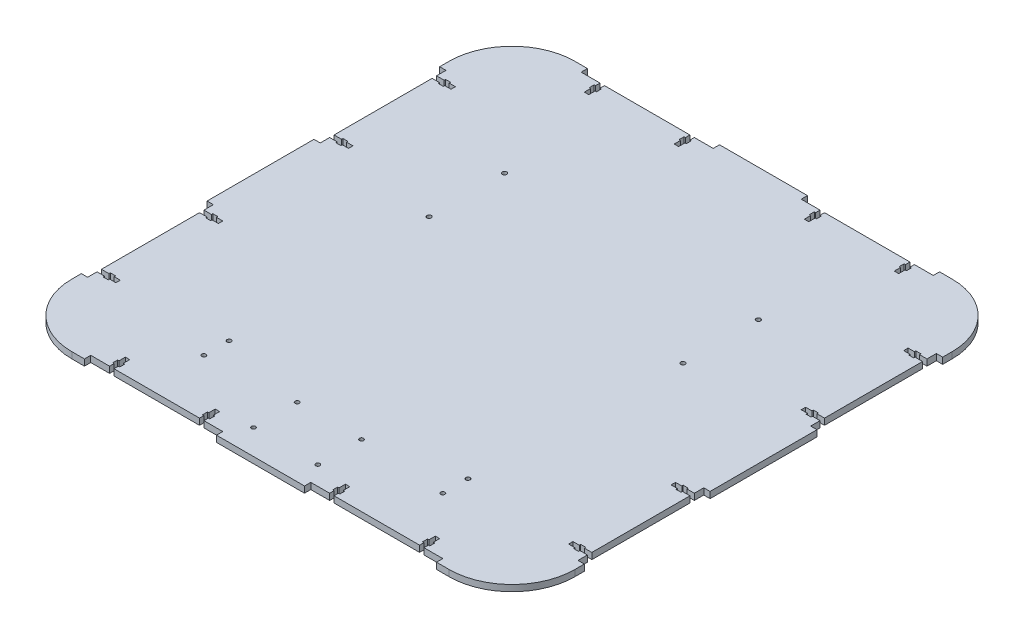
SolidWorks part; units mm, degrees
ref_plane "Front Plane" through (0, 0, 0) normal (0, 0, 1) x (1, 0, 0)
ref_plane "Top Plane" through (0, 0, 0) normal (0, 1, 0) x (1, 0, 0)
ref_plane "Right Plane" through (0, 0, 0) normal (1, 0, 0) x (0, 0, -1)
sketch "Sketch1" plane through (0, 0, 0) normal (0, 1, 0) x (1, 0, 0)
  line L0 (0, -1000) -> (0, 49000) construction
  line L9 (-1000, 0) -> (49000, 0) construction
  line L10 (-10, 190) -> (10, 190) construction
  line L11 (-10, 190) -> (-10, 170) construction
  line L12 (-10, 170) -> (10, 170) construction
  line L13 (10, 190) -> (10, 170) construction
  line L14 (-1010, 180) -> (48990, 180) construction
  line L15 (-1010, -180) -> (48990, -180) construction
  line L16 (0, 1000) -> (0, -49000) construction
  line L17 (-10, -170) -> (10, -170)
  line L18 (10, -190) -> (10, -170)
  line L19 (-10, -190) -> (10, -190)
  line L20 (-10, -190) -> (-10, -170)
  line L22 (-200, 200) -> (200, 200)
  line L23 (-200, 200) -> (-200, -200)
  line L24 (-200, -200) -> (200, -200)
  line L25 (200, 200) -> (200, -200)
  circle A0 centre (0, 0) radius 200 construction
  circle A1 centre (-7.5, 187.5) radius 1.75 construction
  circle A2 centre (7.5, 187.5) radius 1.75 construction
  circle A3 centre (7.5, 172.5) radius 1.75 construction
  circle A4 centre (-7.5, 172.5) radius 1.75 construction
  circle A5 centre (7.5, -187.5) radius 1.75
  circle A6 centre (-7.5, -187.5) radius 1.75
  circle A7 centre (-7.5, -172.5) radius 1.75
  circle A8 centre (7.5, -172.5) radius 1.75
  point P19 (0, 190)
  point P22 (-10, 180)
  dimension "D1" = 400
  dimension "D7" = 3.5
  dimension "D5" = 20
  dimension "D6" = 180
  dimension "D8" = 2.5
  dimension "D9" = 2.5
extrude "Boss-Extrude2" add sketch "Sketch1" along normal blind 5 contours L25 L22 L23 L24 L10 L13 L12 L11 L19 L20 L17 L18 | L20 L19 L18 L17 A6 A5 A7 A8 | L13 L10 L11 L12 A2 A1 A3 A4 region at (0, 0, 180) region at (0, 0, -0.4511)
fillet "Fillet1" radius 50 4 edges at (200, 2.5, -200) (200, 2.5, 200) (-200, 2.5, 200) (-200, 2.5, -200)
sketch "Sketch10" plane through (0, 5, 0) normal (0, 1, 0) x (1, 0, 0)
  line L0 (-150, -200) -> (150, -200) construction
  line L1 (-125, -200) -> (-121.5, -200)
  line L2 (-125, -200) -> (-125, -191.5)
  line L3 (-125, -182.5) -> (-121.5, -182.5)
  line L4 (-121.5, -200) -> (-121.5, -191.5)
  line L6 (-121.5, -187.5) -> (-120.4, -187.5)
  line L7 (-126.1, -187.5) -> (-125, -187.5)
  line L8 (-126.1, -187.5) -> (-126.1, -191.5)
  line L9 (-126.1, -191.5) -> (-125, -191.5)
  line L10 (-120.4, -187.5) -> (-120.4, -191.5)
  line L11 (-121.5, -191.5) -> (-120.4, -191.5)
  line L12 (-125, -187.5) -> (-125, -182.5)
  line L13 (-121.5, -187.5) -> (-121.5, -182.5)
  line L14 (-125, -187.5) -> (-121.5, -187.5) construction
  line L15 (-121.5, -191.5) -> (-125, -191.5) construction
  line L16 (-53.5, -200) -> (-50, -200)
  line L17 (-50, -200) -> (-50, -191.5)
  line L18 (-50, -191.5) -> (-48.9, -191.5)
  line L19 (-48.9, -187.5) -> (-48.9, -191.5)
  line L20 (-50, -187.5) -> (-48.9, -187.5)
  line L21 (-50, -187.5) -> (-50, -182.5)
  line L22 (-53.5, -182.5) -> (-50, -182.5)
  line L23 (-53.5, -187.5) -> (-53.5, -182.5)
  line L24 (-54.6, -187.5) -> (-53.5, -187.5)
  line L25 (-54.6, -187.5) -> (-54.6, -191.5)
  line L26 (-54.6, -191.5) -> (-53.5, -191.5)
  line L27 (-53.5, -200) -> (-53.5, -191.5)
  line L28 (-50, -191.5) -> (-53.5, -191.5) construction
  line L29 (-53.5, -187.5) -> (-50, -187.5) construction
  line L30 (0, -1200) -> (0, 48800) construction
  line L31 (-200, 150) -> (-200, -150) construction
  line L32 (121.5, -191.5) -> (125, -191.5) construction
  line L33 (125, -187.5) -> (121.5, -187.5) construction
  line L34 (125, -200) -> (125, -191.5)
  line L35 (126.1, -191.5) -> (125, -191.5)
  line L36 (126.1, -187.5) -> (126.1, -191.5)
  line L37 (126.1, -187.5) -> (125, -187.5)
  line L38 (125, -187.5) -> (125, -182.5)
  line L39 (125, -182.5) -> (121.5, -182.5)
  line L40 (121.5, -187.5) -> (121.5, -182.5)
  line L41 (121.5, -187.5) -> (120.4, -187.5)
  line L42 (120.4, -187.5) -> (120.4, -191.5)
  line L43 (121.5, -191.5) -> (120.4, -191.5)
  line L44 (121.5, -200) -> (121.5, -191.5)
  line L45 (125, -200) -> (121.5, -200)
  line L46 (53.5, -187.5) -> (50, -187.5) construction
  line L47 (50, -191.5) -> (53.5, -191.5) construction
  line L48 (53.5, -200) -> (53.5, -191.5)
  line L49 (54.6, -191.5) -> (53.5, -191.5)
  line L50 (54.6, -187.5) -> (54.6, -191.5)
  line L51 (54.6, -187.5) -> (53.5, -187.5)
  line L52 (53.5, -187.5) -> (53.5, -182.5)
  line L53 (53.5, -182.5) -> (50, -182.5)
  line L54 (50, -187.5) -> (50, -182.5)
  line L55 (50, -187.5) -> (48.9, -187.5)
  line L56 (48.9, -187.5) -> (48.9, -191.5)
  line L57 (50, -191.5) -> (48.9, -191.5)
  line L58 (50, -200) -> (50, -191.5)
  line L59 (53.5, -200) -> (50, -200)
  line L60 (-1000, 0) -> (49000, 0) construction
  line L61 (125, 200) -> (121.5, 200)
  line L62 (121.5, 200) -> (121.5, 191.5)
  line L63 (121.5, 191.5) -> (120.4, 191.5)
  line L64 (120.4, 187.5) -> (120.4, 191.5)
  line L65 (121.5, 187.5) -> (120.4, 187.5)
  line L66 (121.5, 187.5) -> (121.5, 182.5)
  line L67 (125, 182.5) -> (121.5, 182.5)
  line L68 (125, 187.5) -> (125, 182.5)
  line L69 (126.1, 187.5) -> (125, 187.5)
  line L70 (126.1, 187.5) -> (126.1, 191.5)
  line L71 (126.1, 191.5) -> (125, 191.5)
  line L72 (125, 200) -> (125, 191.5)
  line L73 (53.5, 200) -> (50, 200)
  line L74 (50, 200) -> (50, 191.5)
  line L75 (50, 191.5) -> (48.9, 191.5)
  line L76 (48.9, 187.5) -> (48.9, 191.5)
  line L77 (50, 187.5) -> (48.9, 187.5)
  line L78 (50, 187.5) -> (50, 182.5)
  line L79 (53.5, 182.5) -> (50, 182.5)
  line L80 (53.5, 187.5) -> (53.5, 182.5)
  line L81 (54.6, 187.5) -> (53.5, 187.5)
  line L82 (54.6, 187.5) -> (54.6, 191.5)
  line L83 (54.6, 191.5) -> (53.5, 191.5)
  line L84 (53.5, 200) -> (53.5, 191.5)
  line L85 (-53.5, 200) -> (-53.5, 191.5)
  line L86 (-54.6, 191.5) -> (-53.5, 191.5)
  line L87 (-54.6, 187.5) -> (-54.6, 191.5)
  line L88 (-54.6, 187.5) -> (-53.5, 187.5)
  line L89 (-53.5, 187.5) -> (-53.5, 182.5)
  line L90 (-53.5, 182.5) -> (-50, 182.5)
  line L91 (-50, 187.5) -> (-50, 182.5)
  line L92 (-50, 187.5) -> (-48.9, 187.5)
  line L93 (-48.9, 187.5) -> (-48.9, 191.5)
  line L94 (-50, 191.5) -> (-48.9, 191.5)
  line L95 (-50, 200) -> (-50, 191.5)
  line L96 (-53.5, 200) -> (-50, 200)
  line L97 (-125, 200) -> (-125, 191.5)
  line L98 (-126.1, 191.5) -> (-125, 191.5)
  line L99 (-126.1, 187.5) -> (-126.1, 191.5)
  line L100 (-126.1, 187.5) -> (-125, 187.5)
  line L101 (-125, 187.5) -> (-125, 182.5)
  line L102 (-125, 182.5) -> (-121.5, 182.5)
  line L103 (-121.5, 187.5) -> (-121.5, 182.5)
  line L104 (-121.5, 187.5) -> (-120.4, 187.5)
  line L105 (-120.4, 187.5) -> (-120.4, 191.5)
  line L106 (-121.5, 191.5) -> (-120.4, 191.5)
  line L107 (-121.5, 200) -> (-121.5, 191.5)
  line L108 (-125, 200) -> (-121.5, 200)
  point P11 (-123.25, -200)
  point P15 (-123.25, -191.5)
  point P16 (-123.25, -187.5)
  point P17 (-123.25, -182.5)
  point P33 (0, -200)
  dimension "D1" = 3.5
  dimension "D2" = 5.7
  dimension "D3" = 5
  dimension "D4" = 4
  dimension "D5" = 1.1
  dimension "D7" = 75
  dimension "D8" = 50
  dimension "D9" = 17.5
  dimension "D6" = 2
extrude "Cut-Extrude8" cut sketch "Sketch10" against normal blind 10
sketch "Sketch11" plane through (0, 5, 0) normal (0, 1, 0) x (1, 0, 0)
  line L0 (-150, -200) -> (-125, -200) construction
  line L1 (-140, -200) -> (-35, -200)
  line L2 (-140, -200) -> (-140, -195)
  line L3 (-140, -195) -> (-35, -195)
  line L4 (-35, -200) -> (-35, -195)
  line L5 (-50, -200) -> (-50, -191.5) construction
  line L6 (-125, -191.5) -> (-125, -200) construction
  line L7 (0, -1200) -> (0, 48800) construction
  line L8 (-50, -200) -> (50, -200) construction
  line L9 (-1200, 0) -> (48800, 0) construction
  line L10 (-200, 150) -> (-200, -150) construction
  line L11 (140, -195) -> (35, -195)
  line L12 (35, -200) -> (35, -195)
  line L13 (140, -200) -> (35, -200)
  line L14 (140, -200) -> (140, -195)
  line L15 (140, 200) -> (140, 195)
  line L16 (140, 200) -> (35, 200)
  line L17 (35, 200) -> (35, 195)
  line L18 (140, 195) -> (35, 195)
  line L19 (-140, 195) -> (-35, 195)
  line L20 (-35, 200) -> (-35, 195)
  line L21 (-140, 200) -> (-35, 200)
  line L22 (-140, 200) -> (-140, 195)
  point P15 (0, -200)
  point P20 (-200, 0)
  dimension "D1" = 5
  dimension "D2" = 15
  dimension "D3" = 15
extrude "Cut-Extrude9" cut sketch "Sketch11" against normal blind 10
sketch "Sketch12" plane through (0, 5, 0) normal (0, 1, 0) x (1, 0, 0)
  line L0 (-200, 150) -> (-200, -150) construction
  line L1 (-200, 135) -> (-189, 135)
  line L2 (-200, 135) -> (-200, 131.5)
  line L3 (-200, 131.5) -> (-189, 131.5)
  line L4 (-180, 135) -> (-180, 131.5)
  line L5 (-200, 53.5) -> (-189, 53.5)
  line L6 (-189, 131.5) -> (-189, 130.4)
  line L7 (-189, 136.1) -> (-185, 136.1)
  line L8 (-189, 136.1) -> (-189, 135)
  line L9 (-189, 130.4) -> (-185, 130.4)
  line L10 (-185, 136.1) -> (-185, 135)
  line L11 (-185, 131.5) -> (-185, 130.4)
  line L12 (-185, 135) -> (-180, 135)
  line L13 (-185, 131.5) -> (-180, 131.5)
  line L14 (-189, 135) -> (-189, 131.5) construction
  line L15 (-185, 131.5) -> (-185, 135) construction
  line L16 (-189, 54.6) -> (-189, 53.5)
  line L17 (-189, 54.6) -> (-185, 54.6)
  line L18 (-185, 54.6) -> (-185, 53.5)
  line L19 (-185, 53.5) -> (-180, 53.5)
  line L20 (-180, 53.5) -> (-180, 50)
  line L21 (-185, 50) -> (-180, 50)
  line L22 (-185, 50) -> (-185, 48.9)
  line L23 (-189, 48.9) -> (-185, 48.9)
  line L24 (-189, 50) -> (-189, 48.9)
  line L25 (-200, 50) -> (-189, 50)
  line L26 (-200, 53.5) -> (-200, 50)
  line L27 (-1200, 0) -> (48800, 0) construction
  line L28 (-200, -53.5) -> (-200, -50)
  line L29 (-200, -50) -> (-189, -50)
  line L30 (-189, -50) -> (-189, -48.9)
  line L31 (-189, -48.9) -> (-185, -48.9)
  line L32 (-185, -50) -> (-185, -48.9)
  line L33 (-185, -50) -> (-180, -50)
  line L34 (-180, -53.5) -> (-180, -50)
  line L35 (-185, -53.5) -> (-180, -53.5)
  line L36 (-185, -54.6) -> (-185, -53.5)
  line L37 (-189, -54.6) -> (-185, -54.6)
  line L38 (-189, -54.6) -> (-189, -53.5)
  line L39 (-200, -53.5) -> (-189, -53.5)
  line L40 (-200, -135) -> (-200, -131.5)
  line L41 (-200, -131.5) -> (-189, -131.5)
  line L42 (-189, -131.5) -> (-189, -130.4)
  line L43 (-189, -130.4) -> (-185, -130.4)
  line L44 (-185, -131.5) -> (-185, -130.4)
  line L45 (-185, -131.5) -> (-180, -131.5)
  line L46 (-180, -135) -> (-180, -131.5)
  line L47 (-185, -135) -> (-180, -135)
  line L48 (-185, -136.1) -> (-185, -135)
  line L49 (-189, -136.1) -> (-185, -136.1)
  line L50 (-189, -136.1) -> (-189, -135)
  line L51 (-200, -135) -> (-189, -135)
  line L52 (0, -1200) -> (0, 48800) construction
  line L53 (-35, -200) -> (35, -200) construction
  line L54 (200, -135) -> (189, -135)
  line L55 (189, -136.1) -> (189, -135)
  line L56 (189, -136.1) -> (185, -136.1)
  line L57 (185, -136.1) -> (185, -135)
  line L58 (185, -135) -> (180, -135)
  line L59 (180, -135) -> (180, -131.5)
  line L60 (185, -131.5) -> (180, -131.5)
  line L61 (185, -131.5) -> (185, -130.4)
  line L62 (189, -130.4) -> (185, -130.4)
  line L63 (189, -131.5) -> (189, -130.4)
  line L64 (200, -131.5) -> (189, -131.5)
  line L65 (200, -135) -> (200, -131.5)
  line L66 (200, -53.5) -> (189, -53.5)
  line L67 (189, -54.6) -> (189, -53.5)
  line L68 (189, -54.6) -> (185, -54.6)
  line L69 (185, -54.6) -> (185, -53.5)
  line L70 (185, -53.5) -> (180, -53.5)
  line L71 (180, -53.5) -> (180, -50)
  line L72 (185, -50) -> (180, -50)
  line L73 (185, -50) -> (185, -48.9)
  line L74 (189, -48.9) -> (185, -48.9)
  line L75 (189, -50) -> (189, -48.9)
  line L76 (200, -50) -> (189, -50)
  line L77 (200, -53.5) -> (200, -50)
  line L78 (200, 53.5) -> (200, 50)
  line L79 (200, 50) -> (189, 50)
  line L80 (189, 50) -> (189, 48.9)
  line L81 (189, 48.9) -> (185, 48.9)
  line L82 (185, 50) -> (185, 48.9)
  line L83 (185, 50) -> (180, 50)
  line L84 (180, 53.5) -> (180, 50)
  line L85 (185, 53.5) -> (180, 53.5)
  line L86 (185, 54.6) -> (185, 53.5)
  line L87 (189, 54.6) -> (185, 54.6)
  line L88 (189, 54.6) -> (189, 53.5)
  line L89 (200, 53.5) -> (189, 53.5)
  line L90 (200, 135) -> (200, 131.5)
  line L91 (200, 131.5) -> (189, 131.5)
  line L92 (189, 131.5) -> (189, 130.4)
  line L93 (189, 130.4) -> (185, 130.4)
  line L94 (185, 131.5) -> (185, 130.4)
  line L95 (185, 131.5) -> (180, 131.5)
  line L96 (180, 135) -> (180, 131.5)
  line L97 (185, 135) -> (180, 135)
  line L98 (185, 136.1) -> (185, 135)
  line L99 (189, 136.1) -> (185, 136.1)
  line L100 (189, 136.1) -> (189, 135)
  line L101 (200, 135) -> (189, 135)
  point P31 (-200, 0)
  point P60 (0, -200)
  dimension "D1" = 20
  dimension "D2" = 3.5
  dimension "D3" = 5.7
  dimension "D4" = 5
  dimension "D5" = 4
  dimension "D6" = 15
  dimension "D7" = 1.1
  dimension "D9" = 50
  dimension "D8" = 2
extrude "Cut-Extrude10" cut sketch "Sketch12" against normal blind 5
sketch "Sketch13" plane through (0, 5, 0) normal (0, 1, 0) x (1, 0, 0)
  line L0 (-200, 150) -> (-200, 135) construction
  line L1 (-200, 142.5) -> (-195, 142.5)
  line L2 (-200, 142.5) -> (-200, 42.5)
  line L3 (-200, 42.5) -> (-195, 42.5)
  line L4 (-195, 142.5) -> (-195, 42.5)
  line L6 (-200, 50) -> (-189, 50) construction
  line L7 (-1200, 0) -> (48800, 0) construction
  line L8 (-200, 50) -> (-200, -50) construction
  line L9 (0, -800) -> (0, 49200) construction
  line L10 (-35, 200) -> (35, 200) construction
  line L11 (-200, -42.5) -> (-195, -42.5)
  line L12 (-195, -142.5) -> (-195, -42.5)
  line L13 (-200, -142.5) -> (-195, -142.5)
  line L14 (-200, -142.5) -> (-200, -42.5)
  line L15 (0, 800) -> (0, -49200) construction
  line L16 (200, -142.5) -> (200, -42.5)
  line L17 (200, -142.5) -> (195, -142.5)
  line L18 (195, -142.5) -> (195, -42.5)
  line L19 (200, -42.5) -> (195, -42.5)
  line L20 (200, 42.5) -> (195, 42.5)
  line L21 (195, 142.5) -> (195, 42.5)
  line L22 (200, 142.5) -> (195, 142.5)
  line L23 (200, 142.5) -> (200, 42.5)
  point P13 (-200, 0)
  point P18 (0, 200)
  dimension "D1" = 7.5
  dimension "D2" = 5
extrude "Cut-Extrude11" cut sketch "Sketch13" against normal blind 5
sketch "Sketch15" plane through (0, 5, 0) normal (0, 1, 0) x (1, 0, 0)
  line L0 (-140, 195) -> (-125, 195) construction
  line L2 (0, -800) -> (0, 49200) construction
  line L3 (-35, 200) -> (35, 200) construction
  circle A0 centre (-100.9, 95) radius 1.75
  circle A2 centre (-100.9, 35) radius 1.75
  circle A4 centre (100.9, 35) radius 1.75
  circle A5 centre (100.9, 95) radius 1.75
  point P10 (0, 200)
  dimension "D1" = 3.5
  dimension "D2" = 60
  dimension "D3" = 201.8
  dimension "D4" = 100
extrude "Cut-Extrude13" cut sketch "Sketch15" against normal blind 10
sketch "Sketch16" plane through (0, 5, 0) normal (0, 1, 0) x (1, 0, 0)
  line L0 (0, -806.5425) -> (0, 49193.4575) construction
  line L1 (-30.585, -140.25) -> (30.585, -140.25) construction
  line L2 (-30.585, -140.25) -> (-30.585, -185) construction
  line L3 (-30.585, -185) -> (30.585, -185) construction
  line L4 (30.585, -140.25) -> (30.585, -185) construction
  line L5 (-1011.9969, -162.625) -> (48988.0031, -162.625) construction
  line L6 (-35, 200) -> (35, 200) construction
  line L7 (-35, -200) -> (35, -200) construction
  circle A0 centre (-25.585, -145.25) radius 1.65
  circle A1 centre (25.585, -145.25) radius 1.65
  circle A2 centre (25.585, -180) radius 1.65
  circle A3 centre (-25.585, -180) radius 1.65
  point P9 (0, -140.25)
  point P12 (-30.585, -162.625)
  point P20 (0, 200)
  dimension "D3" = 3.3
  dimension "D1" = 61.17
  dimension "D2" = 44.75
  dimension "D4" = 5
  dimension "D5" = 5
  dimension "D6" = 15
extrude "Cut-Extrude15" cut sketch "Sketch16" against normal blind 10 contours A2 | A3 | A1 | A0 region at (25.585, 5, 145.25) region at (25.585, 5, 180) region at (-25.585, 5, 180)
sketch "Sketch17" plane through (0, 5, 0) normal (0, 1, 0) x (1, 0, 0)
  line L0 (-53.5, -195) -> (-121.5, -195) construction
  line L1 (-100, -125) -> (-90, -125) construction
  line L2 (-100, -125) -> (-100, -155) construction
  line L3 (-100, -155) -> (-90, -155) construction
  line L4 (-90, -125) -> (-90, -155) construction
  line L5 (0, -1200) -> (0, 48800) construction
  line L6 (-35, -200) -> (35, -200) construction
  line L7 (100, -155) -> (90, -155) construction
  line L8 (90, -125) -> (90, -155) construction
  line L9 (100, -125) -> (90, -125) construction
  line L10 (100, -125) -> (100, -155) construction
  circle A0 centre (-95, -130) radius 1.65
  circle A1 centre (-95, -150) radius 1.65
  circle A2 centre (95, -130) radius 1.65
  circle A3 centre (95, -150) radius 1.65
  point P9 (-95, -125)
  point P16 (0, -200)
  dimension "D1" = 3.3
  dimension "D2" = 3.3
  dimension "D3" = 5
  dimension "D4" = 5
  dimension "D5" = 30
  dimension "D6" = 10
  dimension "D7" = 40
  dimension "D8" = 90
extrude "Cut-Extrude16" cut sketch "Sketch17" against normal blind 10
sketch "Sketch18" plane through (0, 5, 0) normal (0, 1, 0) x (1, 0, 0)
  line L0 (-35, -200) -> (35, -200) construction
  line L1 (-12.5, -167.5) -> (12.5, -167.5)
  line L2 (-12.5, -167.5) -> (-12.5, -192.5)
  line L3 (-12.5, -192.5) -> (12.5, -192.5)
  line L4 (12.5, -167.5) -> (12.5, -192.5)
  point P6 (0, -200)
  point P7 (0, -192.5)
  dimension "D1" = 25
  dimension "D2" = 7.5
extrude "Boss-Extrude3" add sketch "Sketch18" against normal blind 3 contours L2 L1 L4 L3
